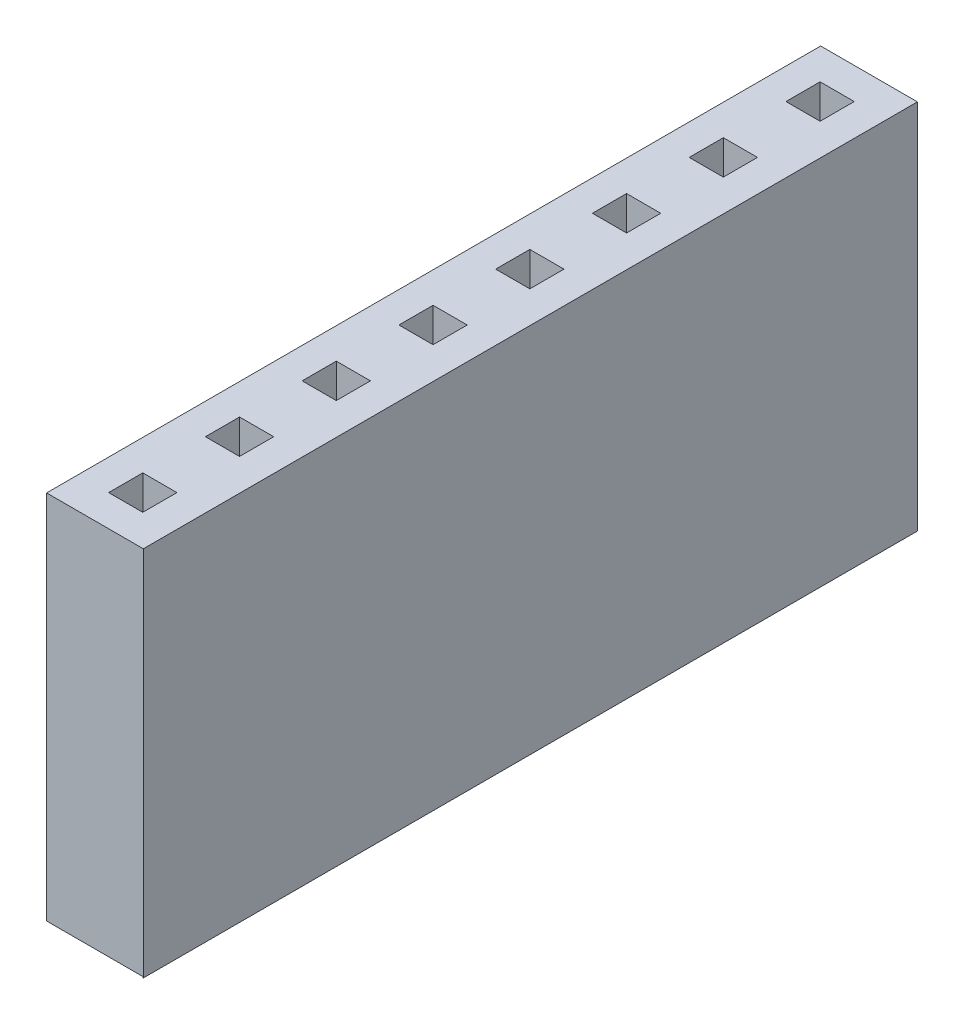
SolidWorks part; units mm, degrees
ref_plane "Front Plane" through (0, 0, 0) normal (0, 0, 1) x (1, 0, 0)
ref_plane "Top Plane" through (0, 0, 0) normal (0, 1, 0) x (1, 0, 0)
ref_plane "Right Plane" through (0, 0, 0) normal (1, 0, 0) x (0, 0, -1)
sketch "Sketch1" plane through (0, 0, 0) normal (0, 1, 0) x (1, 0, 0)
  line L1 (0, 0) -> (2.8333, 0)
  line L2 (0, 0) -> (0, 2.8333)
  line L3 (0, 2.8333) -> (2.8333, 2.8333)
  line L4 (2.8333, 0) -> (2.8333, 2.8333)
  dimension "D1" = 2.8333
other "AlignGroup1"
other "AlignGroup2"
extrude "Boss-Extrude2" add sketch "Sketch1" along normal blind 11
sketch "Sketch2" plane through (0, 0, 0) normal (0, -1, 0) x (-1, 0, 0)
  line L0 (-2.8333, 1.4167) -> (0.1648, 1.4167) construction
  line L1 (-1.9, 0.9167) -> (-0.9, 0.9167)
  line L2 (-1.9, 0.9167) -> (-1.9, 1.9167)
  line L3 (-1.9, 1.9167) -> (-0.9, 1.9167)
  line L4 (-0.9, 0.9167) -> (-0.9, 1.9167)
  line L5 (-1.9, 0.9167) -> (-0.9, 1.9167) construction
  line L6 (-1.9, 1.9167) -> (-0.9, 0.9167) construction
  line L7 (-2.8333, 0) -> (-2.8333, 2.8333) construction
  line L8 (0, 2.8333) -> (0, 0) construction
  point P0 (-1.4, 1.4167)
  dimension "D1" = 1
  dimension "D2" = 0.9
extrude "Cut-Extrude1" cut sketch "Sketch2" against normal blind 11
sketch "Sketch4" plane through (0, 0, 0) normal (0, -1, 0) x (1, 0, 0)
chamfer "Chamfer7" distance 1 angle 60 4 edges at (1.4, 0, -0.9167) (0.9, 0, -1.4167) (1.4, 0, -1.9167) (1.9, 0, -1.4167)
pattern_linear "LPattern5" count 8 spacing 2.8333 along (0, 0, 1) of "Chamfer7", "Cut-Extrude1", "Boss-Extrude2"
